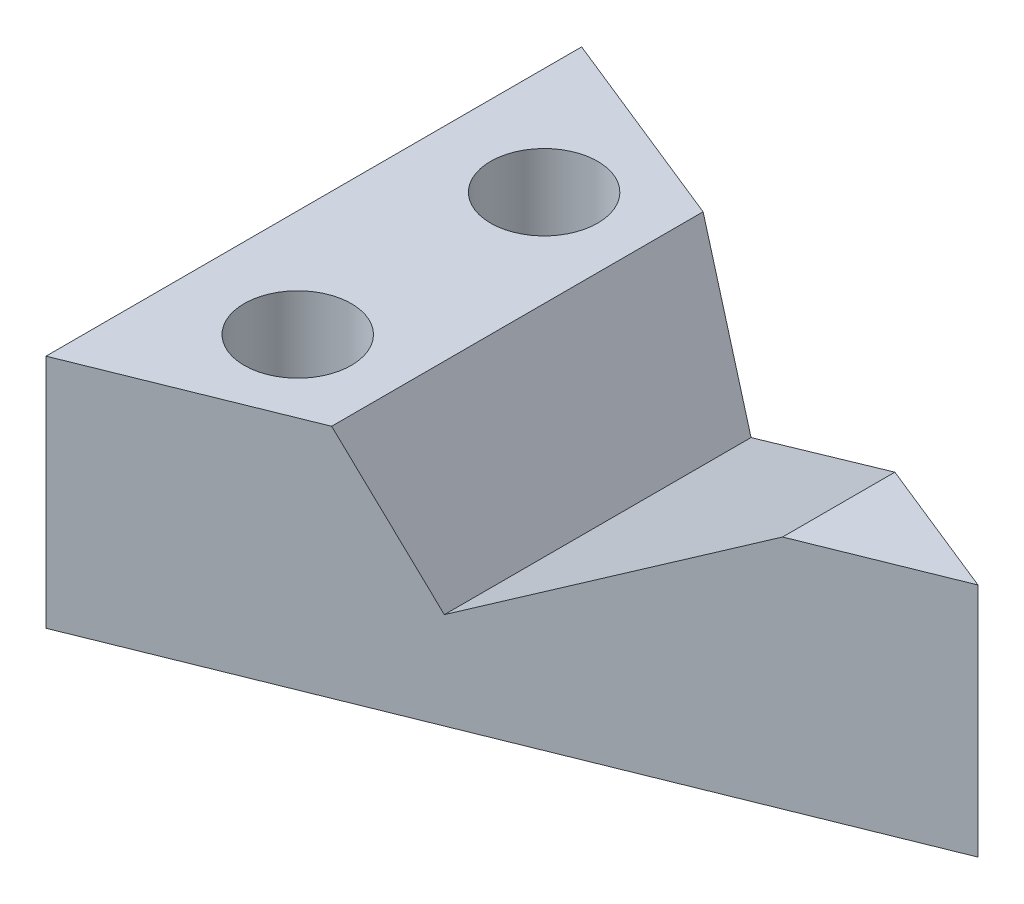
SolidWorks part; units mm, degrees
ref_plane "정면" through (0, 0, 0) normal (0, 0, 1) x (1, 0, 0)
ref_plane "윗면" through (0, 0, 0) normal (0, 1, 0) x (1, 0, 0)
ref_plane "우측면" through (0, 0, 0) normal (1, 0, 0) x (0, 0, -1)
sketch "스케치1" plane through (0, 0, 0) normal (0, 1, 0) x (1, 0, 0)
  line L0 (0, 0) -> (-62, 25)
  line L1 (-62, 25) -> (-62, -25)
  line L2 (-62, -25) -> (0, 0)
  dimension "D1" = 62
  dimension "D2" = 50
extrude "보스-돌출1" add sketch "스케치1" along normal blind 22
sketch "스케치3" plane through (0, 0, 0) normal (0, 0, 1) x (1, 0, 0)
  line L0 (-35.5, 9.0096) -> (-13, 22)
  line L1 (-13, 22) -> (-43, 22)
  line L2 (-43, 22) -> (-35.5, 9.0096)
  line L3 (-62, 22) -> (0, 22) construction
  line L5 (-62, 22) -> (0, 22) construction
  point P3 (0, 0)
  point P8 (0, 0)
  dimension "D1" = 90
  dimension "D2" = 150
  dimension "D3" = 13
  dimension "D4" = 19
extrude "컷-돌출1" cut sketch "스케치3" against normal blind 22 and the other way blind 22
sketch "스케치4" plane through (0, 22, 0) normal (0, 1, 0) x (1, 0, 0)
  line L0 (-62, 25) -> (-62, -25) construction
  circle A0 centre (-52, -11.5) radius 5
  circle A1 centre (-52, 11.5) radius 5
  point P4 (0, 0)
  point P5 (0, 0)
  point P8 (-52.5, 13.9356)
  point P10 (-52, -11.5)
  dimension "D1" = 10
  dimension "D2" = 10
  dimension "D3" = 23
  dimension "D4" = 10
  dimension "D5" = 11.5
  dimension "D6" = 10
extrude "컷-돌출2" cut sketch "스케치4" against normal blind 22
